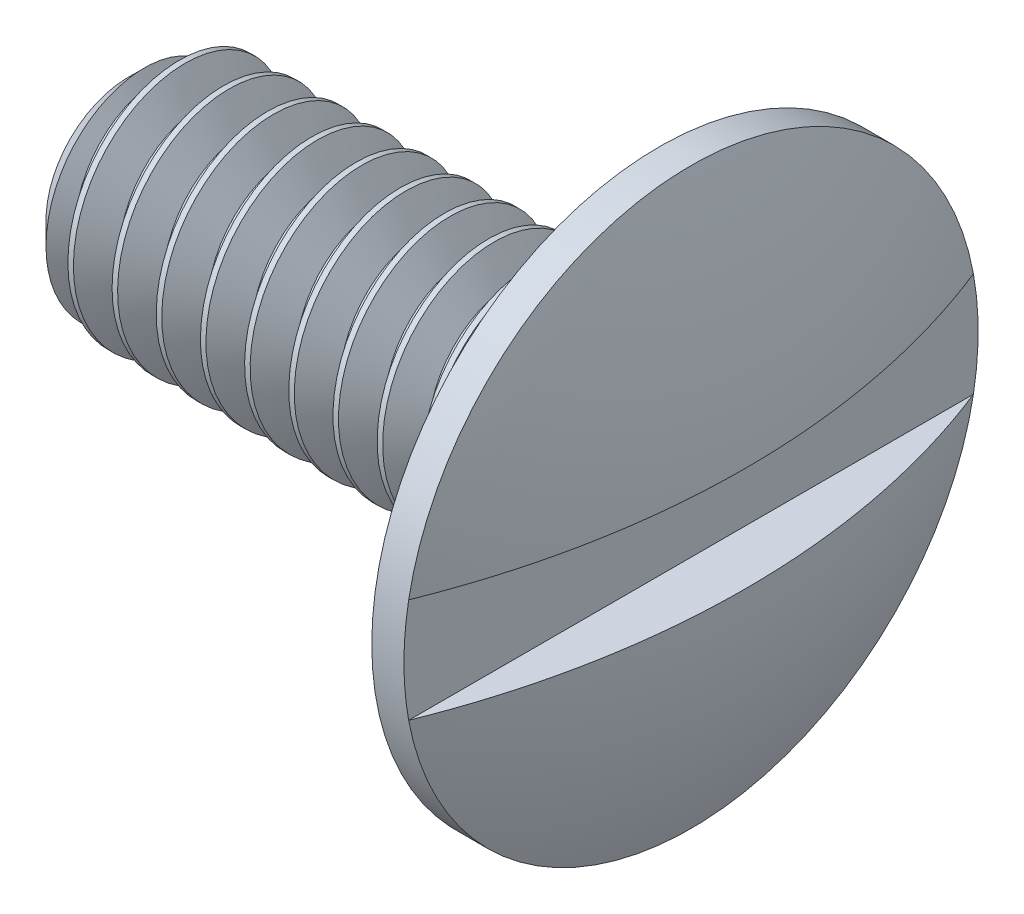
SolidWorks part; units mm, degrees
ref_plane "Front Plane" through (0, 0, 0) normal (0, 0, 1) x (1, 0, 0)
ref_plane "Top Plane" through (0, 0, 0) normal (0, 1, 0) x (1, 0, 0)
ref_plane "Right Plane" through (0, 0, 0) normal (1, 0, 0) x (0, 0, -1)
sketch "Sketch1" plane through (0, 0, 0) normal (0, 0, 1) x (1, 0, 0)
  line L0 (0, 0) -> (9.525, 0) construction
  line L1 (0, 2.0828) -> (0, -2.0828) construction
  line L2 (9.525, 5.1594) -> (9.525, -5.1594) construction
  line L3 (9.525, 0) -> (11.1125, 0) construction
  line L4 (-6.35, 2.5797) -> (-6.35, -2.5797) construction
  line L5 (-6.35, 0) -> (-82.55, 0) construction
  line L6 (-82.55, 5.1594) -> (-82.55, -5.1594) construction
  line L7 (-6.35, 2.0828) -> (-15.875, 2.0828) construction
  line L8 (-15.875, 2.0828) -> (-15.875, -2.0828) construction
  line L9 (-15.875, -2.0828) -> (-6.35, -2.0828) construction
  line L10 (-82.55, 0) -> (-84.1375, 0) construction
  line L11 (9.525, -5.1594) -> (-82.55, -5.1594) construction
  point P18 (-15.875, 0)
  point P19 (-36.5125, -5.1594)
  point P21 (1.9844, -2.0828)
  dimension "Screw Dia" = 4.1656
  dimension "Screw Length" = 9.525
  dimension "Head Dia" = 10.3187
  dimension "Head Height" = 1.5875
  dimension "D1" = 6.35
  dimension "Barrel Dia" = 5.1594
  dimension "Thread Depth" = 9.525
  dimension "Barrel Length" = 76.2
  dimension "D2" = 1.9844
ref_plane "Plane1" through (11.1125, 0, 0) normal (1, 0, 0) x (0, 0, -1)
sketch "Sketch2" plane through (0, 0, 0) normal (1, 0, 0) x (0, 0, -1)
  circle A0 centre (0, 0) radius 2.0828
extrude "Boss-Extrude1" add sketch "Sketch2" along normal up to vertex (9.525 mm away) up to point (9.525, 0, 0)
sketch "Sketch4" plane through (0, 0, 0) normal (-1, 0, 0) x (0, 0, 1)
  circle A1 centre (0, 0) radius 2.0828
  circle A2 centre (0, 0) radius 2.0828
  dimension "D1" = 0
curve "Helix/Spiral1" pitch 0.7937 height 10.3188 turns 13 parameters "Pitch"=0.7937
chamfer "Chamfer1" distance 0.5953 angle 45 1 edges at (0, 0, -2.0828)
sketch "Sketch5" plane through (0, 0, 0) normal (0, 0, 1) x (1, 0, 0)
  line L0 (0, 2.0828) -> (-0.6945, 2.0828)
  line L1 (0, 2.0828) -> (-0.2977, 1.5672)
  line L2 (-0.2977, 1.5672) -> (-0.3969, 1.5672)
  line L3 (-0.3969, 1.5672) -> (-0.6945, 2.0828)
  line L4 (-0.3473, 1.5672) -> (-0.3473, 2.0828) construction
  line L5 (-0.1488, 1.825) -> (-0.5457, 1.825) construction
  dimension "D1" = 0.0992
  dimension "D2" = 0.3969
  dimension "D3" = 60
sweep "Cut-Sweep1" cut profiles "Sketch5" path "Helix/Spiral1" align with end faces yes
sketch "Sketch6" plane through (0, 0, 0) normal (0, 0, 1) x (1, 0, 0)
  line L0 (9.525, 0) -> (9.525, 5.1594)
  line L1 (9.525, 5.1594) -> (10.1023, 5.1594)
  line L2 (11.1125, 0) -> (11.1125, 5.1594) construction
  line L3 (11.1125, 0) -> (9.525, 0) construction
  line L5 (9.525, 0) -> (11.1125, 0)
  line L6 (11.1125, 0) -> (11.1125, -1.9812) construction
  arc A0 (11.1125, 0) -> (10.1023, 5.1594) centre (-2.5674, 0) ccw
  point P10 (11.1125, -1.9812)
  dimension "D1" = 0.5773
revolve "Revolve1" add sketch "Sketch6" angle 360 about L3
ref_plane "Plane2" through (-36.5125, 0, 0) normal (1, 0, 0) x (0, 0, -1)
sketch "Sketch17" plane through (11.1125, 0, 0) normal (1, 0, 0) x (0, 0, -1)
  line L0 (-5.1594, 0) -> (5.1594, 0) construction
  line L1 (-5.1594, 0.9373) -> (5.1594, 0.9373)
  line L2 (-5.1594, 0.9373) -> (-5.1594, -0.9373)
  line L3 (-5.1594, -0.9373) -> (5.1594, -0.9373)
  line L4 (5.1594, 0.9373) -> (5.1594, -0.9373)
  circle A0 centre (0, 0) radius 5.1594 construction
  dimension "D1" = 1.8745
extrude "Cut-Extrude5" cut sketch "Sketch17" against normal up to vertex (1.0102 mm away) up to point (10.1023, 5.1594, 0)
ref_plane "Plane3" through (-6.35, 0, 0) normal (1, 0, 0) x (0, 0, -1)
sketch "Sketch12" plane through (-6.35, 0, 0) normal (1, 0, 0) x (0, 0, -1)
  circle A1 centre (0, 0) radius 2.0828
  circle A2 centre (0, 0) radius 2.0828
  dimension "D1" = 0
curve "Helix/Spiral2" pitch 0.7937 height 10.3188 turns 13
combine bodies "Combine2" operation type add bodies to combine 118 102
equation "\"D1@Sketch5\" = \"Pitch@Helix/Spiral1\"*.125"
equation "\"D2@Sketch5\" = \"Pitch@Helix/Spiral1\"*.50"
equation "\"D3@Helix/Spiral1\" = \"Screw Length@Sketch1\"+\"Pitch@Helix/Spiral1\""
equation "\"D1@Chamfer1\" = \"Pitch@Helix/Spiral1\"*.750"
equation "\"D1@Sketch6\" = \"Head Height@Sketch1\"/2.75"
equation "\"D4@Helix/Spiral2\" =\"Pitch@Helix/Spiral1\""
equation "\"D3@Helix/Spiral2\" = \"Thread Depth@Sketch1\"+\"D4@Helix/Spiral2\""
equation "\"D2@Sketch1\" = \"Pitch@Helix/Spiral1\"*2.50"
equation "\"D1@Sketch17\" = \"Screw Dia@Sketch1\"*.45"
